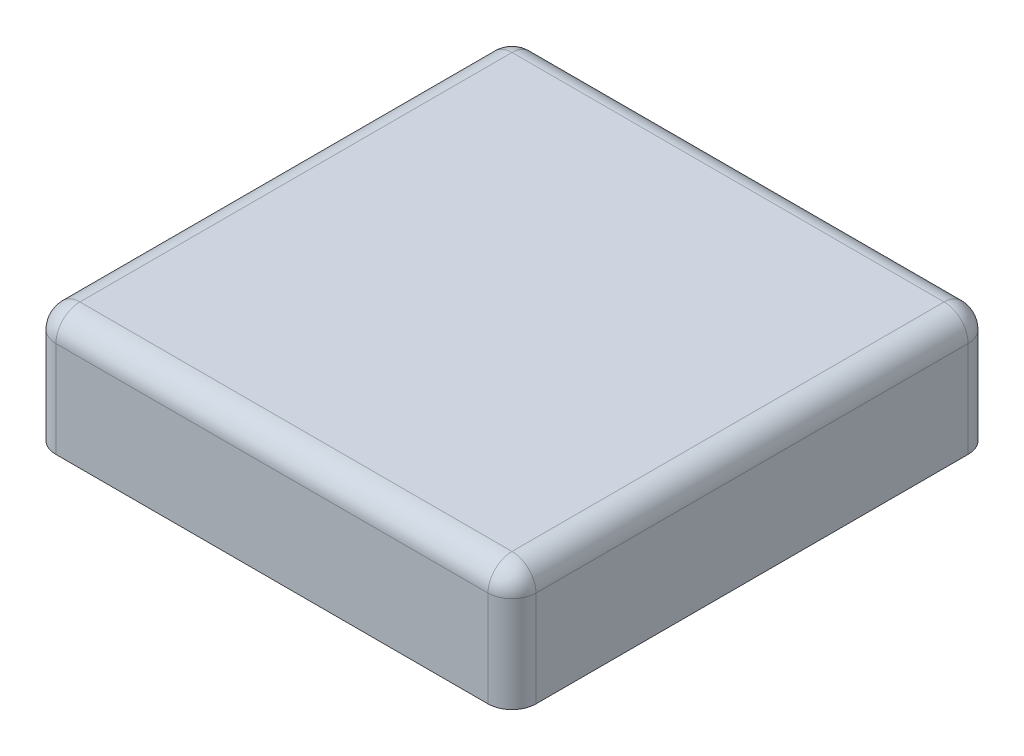
SolidWorks part; units mm, degrees
ref_plane "Front Plane" through (0, 0, 0) normal (0, 0, 1) x (1, 0, 0)
ref_plane "Top Plane" through (0, 0, 0) normal (0, 1, 0) x (1, 0, 0)
ref_plane "Right Plane" through (0, 0, 0) normal (1, 0, 0) x (0, 0, -1)
sketch "Sketch1" plane through (0, 0, 0) normal (0, 1, 0) x (1, 0, 0)
  line L1 (-3, -3) -> (3, -3)
  line L2 (-3, -3) -> (-3, 3)
  line L3 (-3, 3) -> (3, 3)
  line L4 (3, -3) -> (3, 3)
  line L5 (-3, -3) -> (3, 3) construction
  line L6 (-3, 3) -> (3, -3) construction
  point P0 (0, 0)
  dimension "D1" = 6
  dimension "D2" = 6
extrude "Boss-Extrude1" add sketch "Sketch1" along normal blind 1.5
fillet "Fillet1" radius 0.3 8 edges at (3, 0.75, -3) (3, 0.75, 3) (-3, 0.75, -3) (-3, 0.75, 3) (0, 1.5, 3) (0, 1.5, -3) (3, 1.5, 0) (-3, 1.5, 0)
shell "Shell1" thickness 0.3 removed face at (0, 0, 0)
